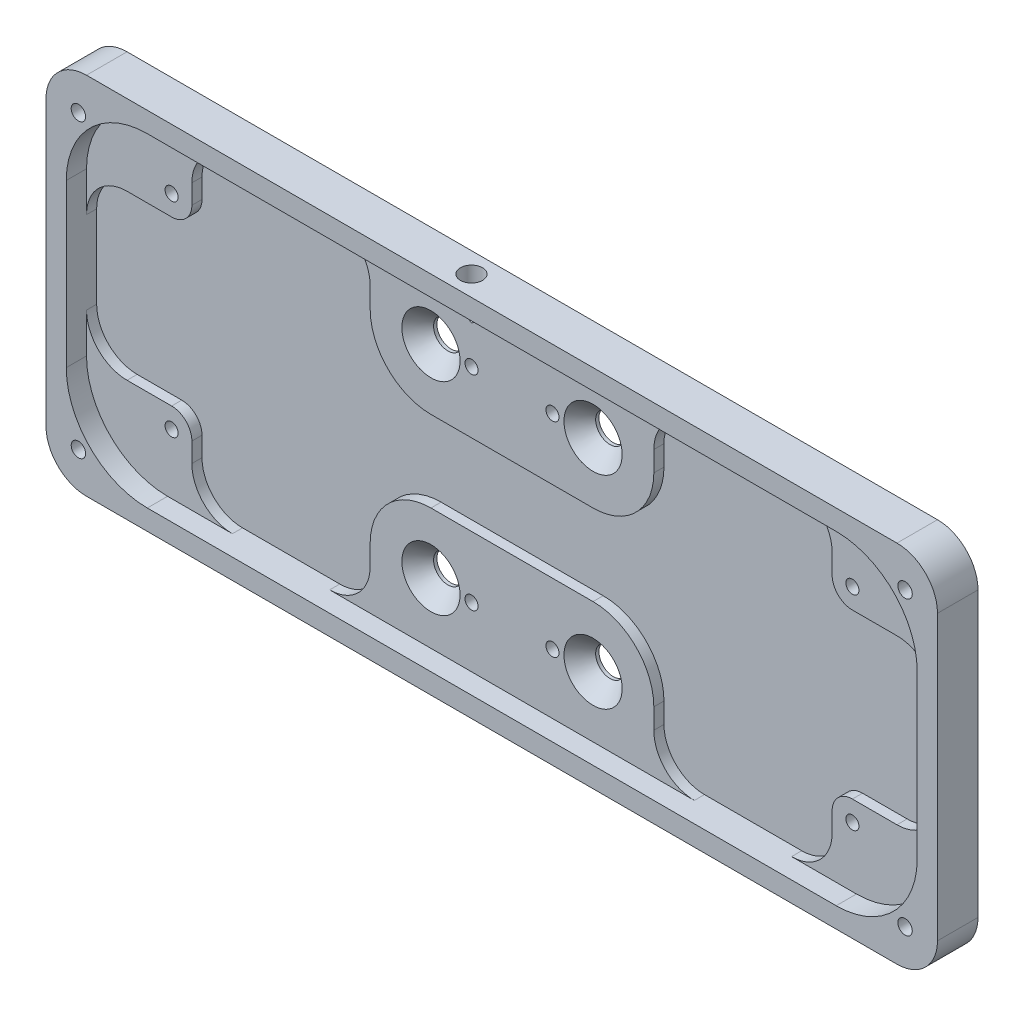
SolidWorks part; units mm, degrees
material "6061-T6 (SS)"
ref_plane "Front Plane" through (0, 0, 0) normal (0, 0, 1) x (1, 0, 0)
ref_plane "Top Plane" through (0, 0, 0) normal (0, 1, 0) x (1, 0, 0)
ref_plane "Right Plane" through (0, 0, 0) normal (1, 0, 0) x (0, 0, -1)
sketch "Sketch1" plane through (0, 0, 0) normal (0, 0, 1) x (1, 0, 0)
  line L1 (-69.85, -28.575) -> (69.85, -28.575)
  line L2 (-69.85, -28.575) -> (-69.85, 28.575)
  line L3 (-69.85, 28.575) -> (69.85, 28.575)
  line L4 (69.85, -28.575) -> (69.85, 28.575)
  line L5 (-69.85, -28.575) -> (69.85, 28.575) construction
  line L6 (-69.85, 28.575) -> (69.85, -28.575) construction
  point P0 (0, 0)
  dimension "D1" = 57.15
  dimension "D2" = 139.7
extrude "Boss-Extrude1" add sketch "Sketch1" along normal mid plane 6.35
sketch "Sketch2" plane through (0, 0, 3.175) normal (0, 0, 1) x (1, 0, 0)
  line L8 (66.675, -25.4) -> (66.675, 25.4)
  line L9 (66.675, 25.4) -> (-66.675, 25.4)
  line L10 (-66.675, 25.4) -> (-66.675, -25.4)
  line L11 (-66.675, -25.4) -> (66.675, -25.4)
  line L12 (66.675, -25.4) -> (66.675, 25.4)
  line L13 (66.675, 25.4) -> (-66.675, 25.4)
  line L14 (-66.675, 25.4) -> (-66.675, -25.4)
  line L15 (-66.675, -25.4) -> (66.675, -25.4)
  dimension "D1" = 3.175
extrude "Cut-Extrude1" cut sketch "Sketch2" against normal blind 3.175
fillet "Fillet1" radius 12.7 4 edges at (66.675, -25.4, 1.5875) (66.675, 25.4, 1.5875) (-66.675, -25.4, 1.5875) (-66.675, 25.4, 1.5875)
fillet "Fillet2" radius 6.35 4 edges at (-69.85, 28.575, 0) (-69.85, -28.575, 0) (69.85, -28.575, 0) (69.85, 28.575, 0)
sketch "Sketch3" plane through (0, 0, 0) normal (0, 0, 1) x (1, 0, 0)
  line L1 (-53.34, -16) -> (53.34, -16) construction
  line L2 (-53.34, -16) -> (-53.34, 16) construction
  line L3 (-53.34, 16) -> (53.34, 16) construction
  line L4 (53.34, -16) -> (53.34, 16) construction
  line L5 (-53.34, -16) -> (53.34, 16) construction
  line L6 (-53.34, 16) -> (53.34, -16) construction
  line L7 (-53.34, 16) -> (-6.34, 16) construction
  line L8 (-53.34, 16) -> (-53.34, -16) construction
  line L9 (-53.34, -16) -> (-6.34, -16) construction
  line L10 (-6.34, 16) -> (-6.34, -16) construction
  line L11 (53.34, 16) -> (6.34, 16) construction
  line L12 (53.34, 16) -> (53.34, -16) construction
  line L13 (53.34, -16) -> (6.34, -16) construction
  line L14 (6.34, 16) -> (6.34, -16) construction
  point P0 (0, 0)
  dimension "D1" = 32
  dimension "D2" = 106.68
  dimension "D3" = 47
  dimension "D4" = 47
hole_wizard "M2.5x0.45 Tapped Hole1" positions "Sketch5" profile "Sketch6" tap size "M2.5x0.45" standard "Ansi Metric" end condition up to next
sketch "Sketch5" plane through (0, 0, 0) normal (0, 0, 1) x (1, 0, 0)
  point P1 (-53.34, -16)
  point P4 (-53.34, 16)
  point P7 (-6.34, 16)
  point P10 (-6.34, -16)
  point P13 (6.34, 16)
  point P16 (6.34, -16)
  point P19 (53.34, 16)
  point P22 (53.34, -16)
sketch "Sketch6" plane through (-53.34, -16, 0) normal (1, 0, 0) x (0, -1, 0)
  line L0 (0, 0) -> (0, 3.175)
  line L1 (0, 3.175) -> (1.025, 3.175)
  line L2 (1.025, 3.175) -> (1.025, 0)
  line L5 (1.025, 0) -> (0, 0)
  line L11 (0, -6.35) -> (0, 107.95) construction
  dimension "Thru Tap Drill Dia." = 2.05
  dimension "Thru Tap Drill Depth" = 3.175
cosmetic thread "Hole Thread1" parameters "D2"=2.5
cosmetic thread "Hole Thread2" parameters "D2"=2.5
cosmetic thread "Hole Thread7" parameters "D2"=2.5
cosmetic thread "Hole Thread8" parameters "D2"=2.5
cosmetic thread "Hole Thread9" parameters "D2"=2.5
cosmetic thread "Hole Thread10" parameters "D2"=2.5
cosmetic thread "Hole Thread11" parameters "D2"=2.5
cosmetic thread "Hole Thread12" parameters "D2"=2.5
hole_wizard "CSK for #8 Flat Head Socket Cap Screw1" positions "Sketch11" profile "Sketch10" countersink size "#8" standard "Ansi Inch" end condition through all
sketch "Sketch11" plane through (0, 0, 0) normal (0, 0, 1) x (1, 0, 0)
  line L1 (-12.7, -15.875) -> (12.7, -15.875)
  line L2 (-12.7, -15.875) -> (-12.7, 15.875)
  line L3 (-12.7, 15.875) -> (12.7, 15.875)
  line L4 (12.7, -15.875) -> (12.7, 15.875)
  line L5 (-12.7, -15.875) -> (12.7, 15.875) construction
  line L6 (-12.7, 15.875) -> (12.7, -15.875) construction
  point P0 (-12.7, 15.875)
  point P74 (0, 0)
  point P76 (12.7, 15.875)
  point P78 (-12.7, -15.875)
  point P80 (12.7, -15.875)
  dimension "D1" = 31.75
  dimension "D2" = 25.4
sketch "Sketch10" plane through (-12.7, 15.875, 0) normal (1, 0, 0) x (0, -1, 0)
  line L0 (0, 0) -> (0, 3.175)
  line L1 (0, 3.175) -> (2.2479, 3.175)
  line L2 (2.2479, 3.175) -> (2.2479, 2.659)
  line L3 (2.2479, 2.659) -> (4.5593, 0)
  line L5 (4.5593, 0) -> (0, 0)
  line L6 (-2.2479, 2.659) -> (-4.5593, 0) construction
  line L11 (0, -6.35) -> (0, 107.95) construction
  dimension "Thru Hole Dia." = 4.4958
  dimension "Thru Hole Depth" = 3.175
  dimension "Near C'Sink Dia." = 9.1186
  dimension "Near C'Sink Angle" = 82
hole_wizard "#4-40 Tapped Hole1" positions "Sketch13" profile "Sketch12" tap size "#4-40" standard "Ansi Inch"
sketch "Sketch13" plane through (0, 0, 3.175) normal (0, 0, 1) x (1, 0, 0)
  line L1 (64.77, -22.86) -> (-64.77, -22.86)
  line L2 (64.77, -22.86) -> (64.77, 22.86)
  line L3 (64.77, 22.86) -> (-64.77, 22.86)
  line L4 (-64.77, -22.86) -> (-64.77, 22.86)
  line L5 (64.77, -22.86) -> (-64.77, 22.86) construction
  line L6 (64.77, 22.86) -> (-64.77, -22.86) construction
  point P0 (-64.77, 22.86)
  point P102 (-64.77, -22.86)
  point P104 (64.77, 22.86)
  point P106 (64.77, -22.86)
  point P114 (0, 0)
  dimension "D1" = 129.54
  dimension "D2" = 45.72
sketch "Sketch12" plane through (-64.77, 22.86, 3.175) normal (1, 0, 0) x (0, -1, 0)
  line L0 (0, 0) -> (0, 8.2992)
  line L1 (0, 8.2992) -> (1.1303, 7.62)
  line L2 (1.1303, 7.62) -> (1.1303, 0)
  line L5 (1.1303, 0) -> (0, 0)
  line L10 (0, 8.2992) -> (-1.1303, 7.62) construction
  line L11 (0, -6.35) -> (0, 107.95) construction
  dimension "Tap Drill Dia." = 2.2606
  dimension "Tap Drill Depth" = 7.62
  dimension "Drill Angle" = 118
cosmetic thread "Hole Thread13" parameters "D1"=5.588, "D2"=2.8448
cosmetic thread "Hole Thread14" parameters "D1"=5.588, "D2"=2.8448
cosmetic thread "Hole Thread15" parameters "D1"=5.588, "D2"=2.8448
cosmetic thread "Hole Thread17" parameters "D1"=5.588, "D2"=2.8448
sketch "Sketch14" plane through (0, 0, 0) normal (0, 0, 1) x (1, 0, 0)
  line L0 (53.975, 25.4) -> (-53.975, 25.4) construction
  line L1 (-22.225, 15.875) -> (-22.225, 25.4)
  line L2 (53.975, 25.4) -> (-53.975, 25.4) construction
  line L5 (0, 0) -> (-66.675, 0)
  line L6 (-66.675, 12.7) -> (-66.675, -12.7) construction
  line L7 (-12.7, 6.35) -> (0, 6.35)
  line L9 (-66.675, 12.7) -> (-66.675, 0)
  line L10 (-53.34, 12.825) -> (-66.6744, 12.825)
  line L12 (-22.225, 25.4) -> (-50.165, 25.4)
  line L13 (-50.165, 16) -> (-50.165, 25.4)
  line L14 (0, 6.35) -> (0, 0)
  arc A0 (-53.34, 12.825) -> (-50.165, 16) centre (-53.34, 16) ccw
  arc A1 (-53.975, 25.4) -> (-66.675, 12.7) centre (-53.975, 12.7) ccw construction
  arc A3 (-66.6744, 12.825) -> (-66.675, 12.7) centre (-53.975, 12.7) ccw
  arc A5 (-22.225, 15.875) -> (-12.7, 6.35) centre (-12.7, 15.875) ccw
  dimension "D1" = 6.35
extrude "Cut-Extrude2" cut sketch "Sketch14" against normal blind 1.5875
mirror "Mirror1" about plane through (0, 0, 0) normal (0, 1, 0) of "Cut-Extrude2"
mirror "Mirror2" about plane through (0, 0, 0) normal (1, 0, 0) of "Mirror1", "Cut-Extrude2"
fillet "Fillet3" radius 6.35 12 edges at (50.165, -25.4, -0.7937) (66.6744, -12.825, -0.7937) (66.6744, 12.825, -0.7937) (50.165, 25.4, -0.7937) (22.225, -25.4, -0.7937) (22.225, 25.4, -0.7937) (-22.225, -25.4, -0.7937) (-50.165, -25.4, -0.7937) (-66.6744, -12.825, -0.7937) (-66.6744, 12.825, -0.7937) (-22.225, 25.4, -0.7937) (-50.165, 25.4, -0.7937)
hole_wizard "#8-32 Tapped Hole1" positions "Sketch16" profile "Sketch15" tap size "#8-32" standard "Ansi Inch"
sketch "Sketch16" plane through (0, 28.575, 0) normal (0, 1, 0) x (-1, 0, 0)
  point P0 (6.35, 0)
  dimension "D1" = 6.35
sketch "Sketch15" plane through (-6.35, 28.575, 0) normal (1, 0, 0) x (0, 0, 1)
  line L0 (0, 0) -> (0, 6.6258)
  line L1 (0, 6.6258) -> (1.7272, 5.588)
  line L2 (1.7272, 5.588) -> (1.7272, 0)
  line L5 (1.7272, 0) -> (0, 0)
  line L10 (0, 6.6258) -> (-1.7272, 5.588) construction
  line L11 (0, -6.35) -> (0, 107.95) construction
  dimension "Tap Drill Dia." = 3.4544
  dimension "Tap Drill Depth" = 5.588
  dimension "Drill Angle" = 118
